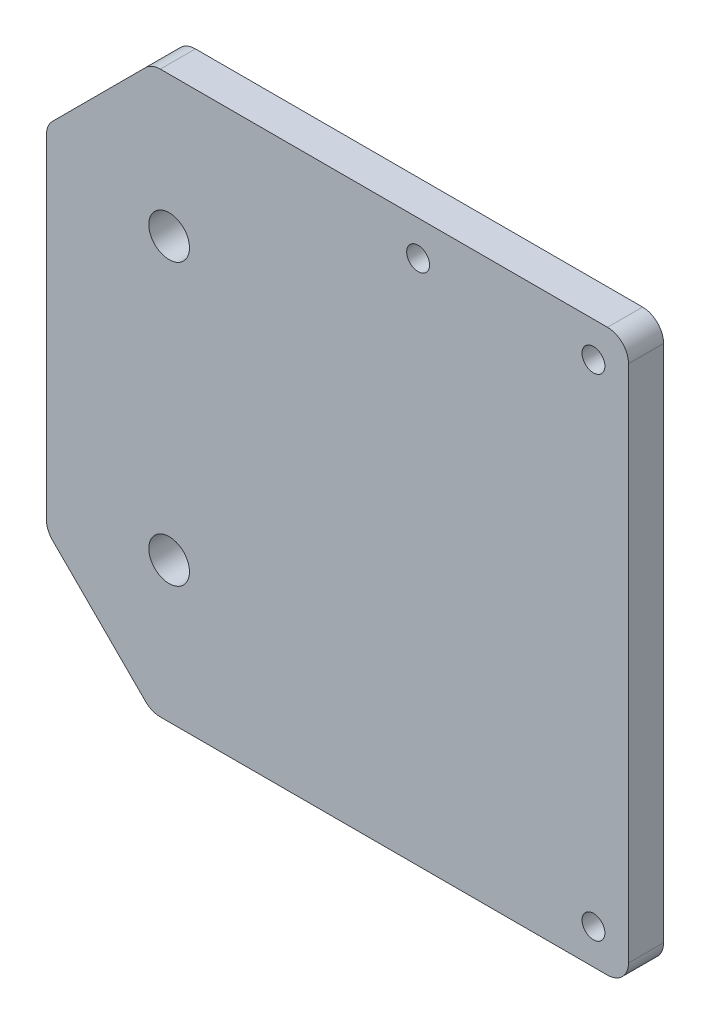
SolidWorks part; units mm, degrees
ref_plane "Front Plane" through (0, 0, 0) normal (0, 0, 1) x (1, 0, 0)
ref_plane "Top Plane" through (0, 0, 0) normal (0, 1, 0) x (1, 0, 0)
ref_plane "Right Plane" through (0, 0, 0) normal (1, 0, 0) x (0, 0, -1)
sketch "Base" plane through (0, 0, 0) normal (0, 0, 1) x (1, 0, 0)
  line L1 (-39.7758, 40) -> (-39.7758, -40)
  line L4 (-17.7758, -40) -> (43.2242, -40)
  line L8 (-22.2758, 20) -> (-22.2758, -20) construction
  line L9 (12.7242, -0.745) -> (12.7242, -28.495) construction
  line L10 (19.7242, -2.87) -> (5.7242, -2.87)
  line L11 (19.7242, -2.87) -> (19.7242, -26.37)
  line L12 (19.7242, -26.37) -> (5.7242, -26.37)
  line L13 (5.7242, -2.87) -> (5.7242, -26.37)
  line L14 (33.2242, 30) -> (33.2242, -30) construction
  line L15 (33.2242, 1) -> (43.2242, 1) construction
  line L16 (43.2242, 40) -> (43.2242, -40)
  line L18 (-17.7758, -40) -> (-39.7758, -40)
  line L19 (33.2242, -30) -> (33.2242, -40) construction
  line L20 (33.2242, 30) -> (43.2242, 40) construction
  line L21 (-39.7758, 40) -> (43.2242, 40)
  line L24 (33.2242, 30) -> (5.7242, 30) construction
  line L25 (5.7242, 30) -> (5.7242, 40) construction
  line L26 (5.7242, -40) -> (5.7242, -30) construction
  line L27 (5.7242, -30) -> (33.2242, -30) construction
  circle A0 centre (12.7242, -20) radius 17.5 construction
  point P2 (30.2242, -20)
  point P7 (24.1741, 0)
  point P9 (12.7242, -40)
  point P10 (-39.7758, 0)
  point P11 (-22.2758, -20)
  point P12 (-22.2758, 20)
  point P15 (-22.2758, 0)
  point P20 (12.7242, -2.87)
  point P22 (19.7242, -14.62)
  point P23 (12.7242, 20)
  point P24 (-22.2758, -20)
  point P25 (-22.2758, 20)
  point P26 (12.7242, -0.745)
  point P27 (12.7242, -28.495)
  point P30 (12.7242, -14.62)
  point P31 (12.7242, -20)
  point P33 (12.7242, -2.5)
  point P41 (38.2242, -35)
  point P43 (38.2242, 35)
  point P44 (13.2242, 35)
  point P45 (5.7242, 35)
  point P46 (38.2242, 1)
  point P47 (33.2242, -35)
  dimension "D11" = 35
  dimension "D2" = 23.5
  dimension "D1" = 14
  dimension "D4" = 35
  dimension "D9" = 27.75
  dimension "D3" = 40
  dimension "D10" = 6.37
  dimension "D5" = 17.5
  dimension "D14" = 10
  dimension "D7" = 80
  dimension "D8" = 10
  dimension "D12" = 3.5
  dimension "D6" = 3
  dimension "D13" = 7.5
sketch "Hole_sketch" plane through (0, 0, 0) normal (0, 0, 1) x (1, 0, 0)
  point P0 (-22.2758, -20)
  point P2 (-22.2758, 20)
  point P4 (12.7242, -0.745)
  point P6 (12.7242, -28.495)
extrude "Main" add sketch "Base" along normal blind 5 contours L18 L4 L16 L1 L13 L10 L11 L12 | L21 | L10 L13 L12 L11 region at (1.1507, 0.7622, 0) region at (12.7242, -14.62, 0)
hole_wizard "Gear Axis Holes" positions "Sketch9" profile "Sketch8" hole size "Ø5.8" standard "ANSI Metric" end condition through all
sketch "Sketch9" plane through (0, 0, 5) normal (0, 0, -1) x (-1, 0, 0)
  point P0 (22.2758, -20)
  point P3 (22.2758, 20)
sketch "Sketch8" plane through (-22.2758, -20, 5) normal (1, 0, 0) x (0, -1, 0)
  line L0 (0, 0) -> (0, 5)
  line L1 (0, 5) -> (2.9, 5)
  line L2 (2.9, 5) -> (2.9, 0)
  line L5 (2.9, 0) -> (0, 0)
  line L11 (0, -6.35) -> (0, 107.95) construction
  dimension "Thru Hole Dia." = 5.8
  dimension "Thru Hole Depth" = 5
sketch "Sketch13" plane through (0, 0, 5) normal (0, 0, 1) x (1, 0, 0)
  line L10 (33.2242, 30) -> (33.2242, -30) construction
  line L11 (33.2242, 30) -> (5.7242, 30) construction
  line L12 (5.7242, 30) -> (5.7242, 40) construction
  line L13 (-39.7758, 40) -> (43.2242, 40) construction
  line L15 (43.2242, 40) -> (43.2242, -40) construction
  line L17 (33.2242, 30) -> (33.2242, 1)
  line L18 (33.2242, 30) -> (5.7242, 30)
  line L19 (5.7242, 30) -> (5.7242, 40)
  line L20 (5.7242, 40) -> (43.2242, 40)
  line L21 (43.2242, 40) -> (43.2242, 1)
  line L22 (33.2242, -30) -> (33.2242, -40) construction
  line L23 (-17.7758, -40) -> (43.2242, -40) construction
  line L24 (33.2242, -30) -> (33.2242, -40)
  line L25 (33.2242, 30) -> (33.2242, -30)
  line L26 (33.2242, -40) -> (43.2242, -40)
  line L27 (43.2242, 40) -> (43.2242, -40)
chamfer "Chamfer1" distance 15 angle 45 2 edges at (-39.7758, -40, 2.5) (-39.7758, 40, 2.5)
fillet "Fillet6" radius 3 6 edges at (-24.7758, -40, 2.5) (-39.7758, -25, 2.5) (-39.7758, 25, 2.5) (-24.7758, 40, 2.5) (43.2242, 40, 2.5) (43.2242, -40, 2.5)
hole_wizard "#4 Clearance Hole1" positions "Sketch15" profile "Sketch14" hole size "#4" standard "ANSI Inch" end condition through all
sketch "Sketch15" plane through (0, 0, 5) normal (0, 0, 1) x (1, 0, 0)
  point P1 (13.2242, 35)
  point P3 (38.2242, 35)
  point P5 (38.2242, -35)
sketch "Sketch14" plane through (13.2242, 35, 5) normal (1, 0, 0) x (0, -1, 0)
  line L0 (0, 0) -> (0, 5)
  line L1 (0, 5) -> (1.6319, 5)
  line L2 (1.6319, 5) -> (1.6319, 0)
  line L5 (1.6319, 0) -> (0, 0)
  line L11 (0, -6.35) -> (0, 107.95) construction
  dimension "Thru Hole Dia." = 3.2639
  dimension "Thru Hole Depth" = 5
equation "\"D_gear-axes\"= 40mm"
equation "\"D_gear-servo\"= 35mm"
equation "\"W_servo\"= 23mm"
equation "\"W_servo-center\"= 6.37mm"
equation "\"D1@Base\"=\"L_servo\"+1"
equation "\"D2@Base\"=\"W_servo\"+0.5"
equation "\"L_servo\"= 13mm"
equation "\"D4@Base\" = \"D_gear-servo\""
equation "\"D9@Base\"=27.75"
equation "\"D_servo-holes\"= 3.1mm"
equation "\"D3@Base\"=\"D_gear-axes\""
equation "\"D10@Base\"=\"W_servo-center\""
